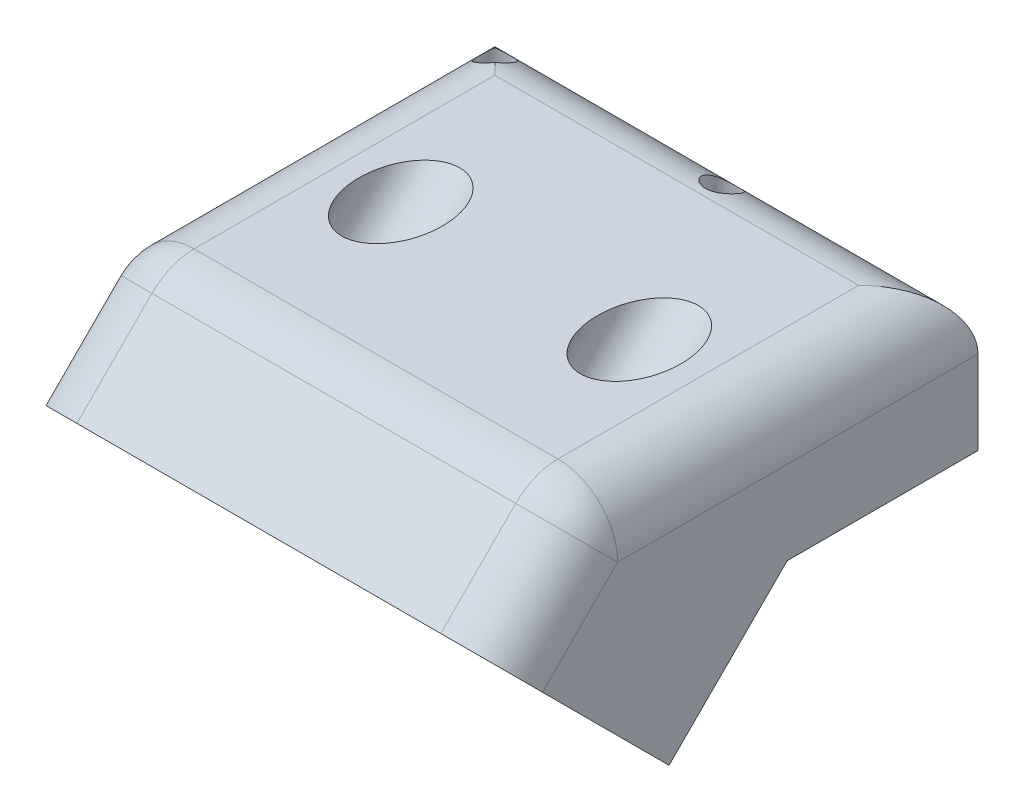
SolidWorks part; units mm, degrees
ref_plane "Front Plane" through (0, 0, 0) normal (0, 0, 1) x (1, 0, 0)
ref_plane "Top Plane" through (0, 0, 0) normal (0, 1, 0) x (1, 0, 0)
ref_plane "Right Plane" through (0, 0, 0) normal (1, 0, 0) x (0, 0, -1)
sketch "Sketch1" plane through (0, 0, 0) normal (0, 1, 0) x (1, 0, 0)
  line L0 (-20.25, 5) -> (20.25, 5) construction
  line L1 (-20.25, -8) -> (20.25, -8)
  line L2 (-20.25, -8) -> (-20.25, 8)
  line L3 (-20.25, 8) -> (20.25, 8)
  line L4 (20.25, -8) -> (20.25, 8)
  line L5 (-20.25, -8) -> (20.25, 8) construction
  line L6 (-20.25, 8) -> (20.25, -8) construction
  line L8 (-18.25, -6) -> (18.25, -6)
  line L9 (-18.25, -6) -> (-18.25, 6)
  line L10 (-18.25, 6) -> (18.25, 6)
  line L11 (18.25, -6) -> (18.25, 6)
  line L12 (-18.25, -6) -> (18.25, 6) construction
  line L13 (-18.25, 6) -> (18.25, -6) construction
  circle A0 centre (-17.25, 5) radius 1.35
  circle A1 centre (1.75, 5) radius 1.35
  circle A2 centre (-17.25, 5) radius 3
  circle A3 centre (1.75, 5) radius 3
  point P0 (0, 0)
  point P12 (0, 0)
  dimension "D4" = 2.7
  dimension "D5" = 2.7
  dimension "D1" = 40.5
  dimension "D2" = 16
  dimension "D3" = 3
  dimension "D6" = 3
  dimension "D7" = 19
  dimension "D8" = 2
  dimension "D9" = 2
extrude "Boss-Extrude1" add sketch "Sketch1" along normal blind 12 contours A3 L10 L11 L8 L9 A2 L2 L1 L4 L3 | L9 A2 L10 A0 | A3 L3 A2 L10 | L10 A2 L9 A0 | A2 L3 L2 | L10 A3 A1 | L10 A3 A1 | A0 L10 L9 region at (-19.8145, 0, 1.5) region at (-19.5799, 0, -7.3299) region at (-19.313, 0, -7.063) region at (-7.75, 0, -7.0476) region at (-16.0537, 0, -3.8037) region at (1.75, 0, -6.8667) region at (4.6357, 0, -5.4951) region at (-18.2195, 0, -5.9695)
extrude "Boss-Extrude2" add sketch "Sketch1<3>" along normal blind 10 from offset 2 contours A3 L10 A2 L9 L8 L11 region at (0.481, 0, 0.355)
sketch "Sketch1<3>" plane through (0, 0, 0) normal (0, 1, 0) x (1, 0, 0) same geometry as "Sketch1"
sketch "Sketch3" plane through (-20.25, 0, 0) normal (-1, 0, 0) x (0, 0, 1)
  line L0 (8, 0) -> (17.8995, -9.8995)
  line L1 (8, 0) -> (-8, 0) construction
  line L2 (17.8995, -9.8995) -> (32.0416, 4.2426)
  line L3 (32.0416, 4.2426) -> (24.2843, 12)
  line L4 (24.2843, 12) -> (8, 12)
  line L5 (8, 12) -> (-8, 12) construction
  line L6 (8, 12) -> (8, 0)
  dimension "D1" = 135
  dimension "D2" = 14
  dimension "D3" = 20
extrude "Boss-Extrude3" add sketch "Sketch3" against normal up to surface (40.5 mm away) up to face at (20.25, 6, 0)
sketch "Sketch4" plane through (0, -13.8995, 13.8995) normal (0, -0.7071, 0.7071) x (1, 0, 0)
  line L0 (10.9119, 15.6569) -> (-29.5881, 15.6569) construction
  line L3 (0, 13.6375) -> (0, 21.3952) construction
  line L5 (20.25, 25.6569) -> (-20.25, 25.6569) construction
  line L6 (20.25, 25.6569) -> (20.25, 5.6569) construction
  circle A0 centre (10, 15.6569) radius 3.5
  circle A1 centre (-10, 15.6569) radius 3.5
  circle A2 centre (10, 15.6569) radius 2
  circle A3 centre (-10, 15.6569) radius 2
  point P4 (0, 25.6569)
  point P11 (20.25, 15.6569)
  dimension "D1" = 10
  dimension "D2" = 7
  dimension "D3" = 4
  dimension "D4" = 4
extrude "Cut-Extrude3" cut sketch "Sketch4" against normal through all contours A3 | A2 region at (10, -2.8284, 24.9706) region at (-10, -2.8284, 24.9706)
extrude "Cut-Extrude4" cut sketch "Sketch4<5>" against normal through all from offset 3 offset against normal yes
sketch "Sketch4<5>" plane through (0, -13.8995, 13.8995) normal (0, -0.7071, 0.7071) x (1, 0, 0) same geometry as "Sketch4"
chamfer "Chamfer2" distance 1 angle 45 2 edges at (10, -2.1213, 21.435) (-10, -2.1213, 21.435)
fillet "Fillet2" radius 5 6 edges at (20.25, 8.1213, 28.163) (-20.25, 8.1213, 28.163) (20.25, 12, 8.1421) (-20.25, 12, 8.1421) (0, 12, 24.2843) (0, 12, -8)
